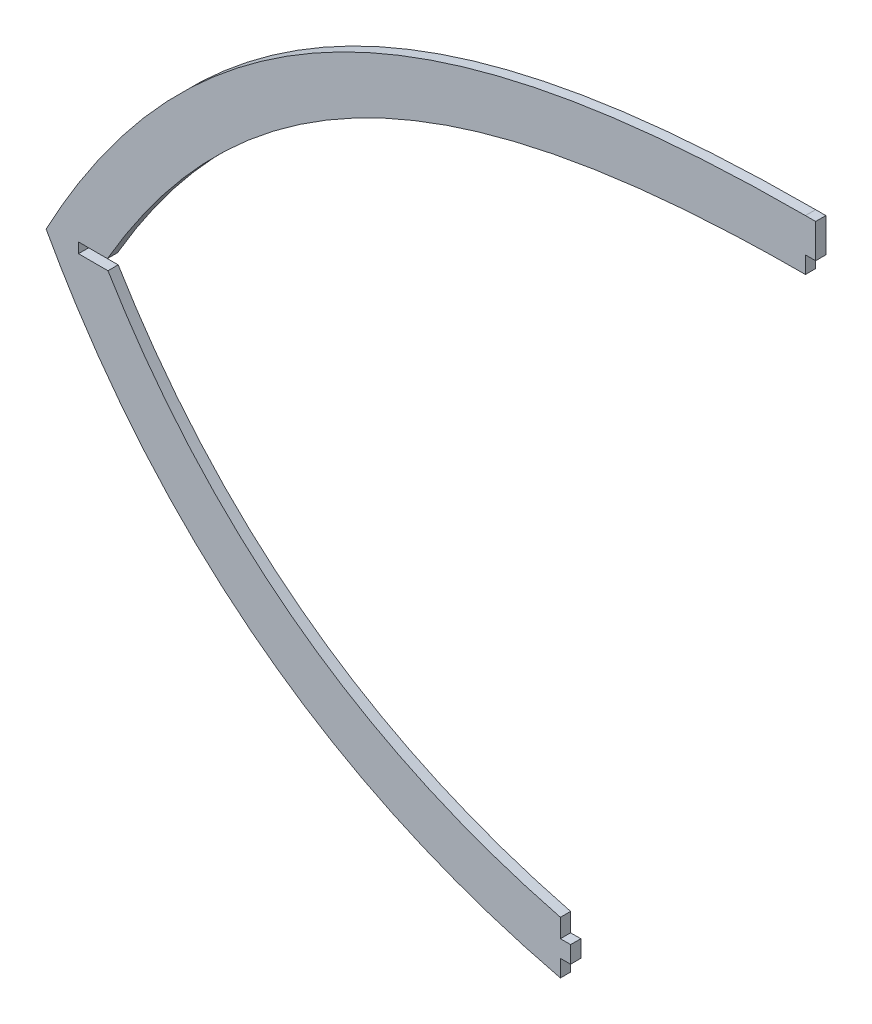
SolidWorks part; units mm, degrees
material "birch 3mm plywood"
ref_plane "Front" through (0, 0, 0) normal (0, 0, 1) x (1, 0, 0)
ref_plane "Top" through (0, 0, 0) normal (0, 1, 0) x (1, 0, 0)
ref_plane "Right" through (0, 0, 0) normal (1, 0, 0) x (0, 0, -1)
sketch "Sketch1" plane through (0, 0, 0) normal (0, 0, 1) x (1, 0, 0)
  line L1 (-83, 160.5) -> (-83, -69.5) construction
  line L2 (-83, 150.5) -> (-80, 150.5)
  line L3 (-80, 150.5) -> (-83, 150.5) construction
  line L4 (-155, -69.5) -> (-155, -64.5)
  line L6 (-155, -69.5) -> (-155, 44) construction
  line L9 (-155, -64.5) -> (-152, -64.5)
  line L12 (-152, -64.5) -> (-152, -59.5)
  line L13 (-152, -59.5) -> (-155, -59.5)
  line L14 (-155, -59.5) -> (-155, -54.0482)
  line L15 (-288.0952, 47) -> (-296.5952, 47)
  line L16 (-83, 47) -> (-305.0917, 47) construction
  line L17 (-296.5952, 47) -> (-296.5952, 44)
  line L18 (-305.0917, 44) -> (-83, 44) construction
  line L19 (-296.5952, 44) -> (-287.9228, 44)
  line L20 (-83, 160.5) -> (-83, 150.5) construction
  line L21 (-83, 160.5) -> (-80, 160.5)
  line L22 (-80, 160.5) -> (-80, 150.5)
  line L23 (-83, 150.5) -> (-83, 145.5)
  line L24 (-155, 43.3771) -> (-155, -69.5) construction
  line L25 (-152, -69.5) -> (-152, 43.3771) construction
  parabola Q0 (-155, -69.5) -> (-306.0893, 45.5) focus (-179.0197, 57.3821) apex (-244.7409, -27.552) construction
  parabola Q1 (-155, -69.5) -> (-306.0893, 45.5) focus (-179.0197, 57.3821) apex (-244.7409, -27.552)
  spline S0 degree 3 poles (912.6271, 67.093) (-173.2309, 29.6899) (-479.3533, 668.8854) (-333.6092, -954.1027) knots -1.973203 -1.973203 -1.973203 -1.973203 2.60577 2.60577 2.60577 2.60577 only from (-83, 160.5) to (-306.0893, 45.5) construction
  spline S1 degree 3 poles (-83, 160.5) (-186.6749, 160.5) (-259.8996, 132.37) (-306.0893, 45.5) knots 0 0 0 0 1 1 1 1
  spline S2 degree 1 poles (-151.4967, -54.9148) (-288.8909, 45.6217) knots 0 0 1 1 construction
  spline S3 degree 1 poles (-83, 145.5) (-288.8909, 45.6217) knots 0 0 1 1 construction
  spline S4 degree 3 poles (-151.4967, -54.9148) (-153.3988, -54.458) (-157.2086, -53.4983) (-164.6601, -51.4419) (-173.7484, -48.594) (-184.2693, -44.7413) (-197.7998, -39.024) (-213.7896, -30.7928) (-231.5494, -19.1756) (-247.9291, -5.7971) (-260.462, 6.8492) (-269.8307, 17.8876) (-276.5289, 26.6314) (-281.8406, 34.3147) (-285.9211, 40.691) (-287.9161, 43.9748) (-288.8909, 45.6217) knots 0.497669 0.497669 0.497669 0.497669 0.497806 0.497943 0.498217 0.498491 0.498765 0.499314 0.499862 0.500411 0.500959 0.501233 0.501508 0.501782 0.501919 0.502056 0.502056 0.502056 0.502056 only from (-155, -54.0482) to (-287.9228, 44)
  spline S5 degree 3 poles (-288.8909, 45.6217) (-288.2118, 46.8068) (-286.8274, 49.1771) (-284.0331, 53.7809) (-280.4563, 59.3452) (-276.0412, 65.7051) (-269.9863, 73.7792) (-262.1032, 83.1283) (-252.1296, 93.2247) (-241.6235, 102.2655) (-226.87, 112.9967) (-206.9505, 124.0773) (-184.8372, 132.3478) (-165.7316, 137.4023) (-150.6813, 140.4388) (-134.8993, 142.7481) (-121.1337, 144.0897) (-109.751, 144.8283) (-101.0301, 145.2187) (-93.6051, 145.4111) (-87.5802, 145.4874) (-84.523, 145.5) (-83, 145.5) knots 0 0 0 0 0.015161 0.030323 0.060645 0.090968 0.12129 0.181936 0.242581 0.303226 0.363871 0.485162 0.606452 0.667098 0.727743 0.788388 0.849033 0.879356 0.909679 0.940001 0.955163 0.970324 0.970324 0.970324 0.970324 only from (-288.0952, 47) to (-83, 145.5)
  point P15 (-80, 151.9206)
  point P17 (-155, -54.0487)
  point P20 (0, 0)
  point P24 (0, 0)
  point P31 (0, 0)
  point P39 (0, 0)
  point P40 (0, 0)
  point P41 (0, 0)
  point P42 (-156.1317, -59.55)
  point P44 (-155, -60.0531)
  point P47 (-152, -60.5562)
  dimension "D3" = 5
  dimension "D4" = 5
  dimension "D5" = 8.5
  dimension "D1" = 15
extrude "Boss-Extrude1" add sketch "Sketch1" along normal mid plane 3 contours S1 Q1 L4 L9 L12 L13 L14 S4 L19 L17 L15 S5 L23 L2 L22 L21
